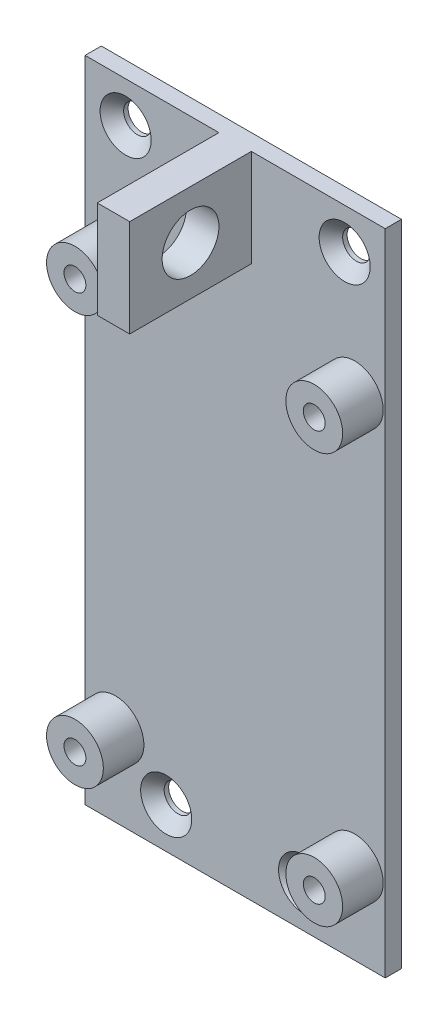
SolidWorks part; units mm, degrees
ref_plane "Plan de face" through (0, 0, 0) normal (0, 0, 1) x (1, 0, 0)
ref_plane "Plan de dessus" through (0, 0, 0) normal (0, 1, 0) x (1, 0, 0)
ref_plane "Plan de droite" through (0, 0, 0) normal (1, 0, 0) x (0, 0, -1)
sketch "Main-Sketch" plane through (0, 0, 0) normal (0, 0, 1) x (1, 0, 0)
  line L1 (0, 0) -> (37, 0)
  line L2 (0, 0) -> (0, 80)
  line L3 (0, 80) -> (37, 80)
  line L4 (37, 0) -> (37, 80)
  dimension "D1" = 37
  dimension "D2" = 80
extrude "Main-Extrusion" add sketch "Main-Sketch" along normal blind 2
sketch "Board-Fix-Sketch" plane through (0, 0, 2) normal (0, 0, 1) x (1, 0, 0)
  line L0 (0, 80) -> (0, 0) construction
  line L1 (37, 0) -> (37, 80) construction
  line L2 (0, 0) -> (37, 0) construction
  circle A0 centre (3.75, 10) radius 3.5
  circle A1 centre (33.25, 10) radius 3.5
  circle A2 centre (33.25, 60.5) radius 3.5
  circle A3 centre (3.75, 60.5) radius 3.5
  circle A4 centre (3.75, 10) radius 1.35
  circle A5 centre (33.25, 10) radius 1.35
  circle A6 centre (33.25, 60.5) radius 1.35
  circle A7 centre (3.75, 60.5) radius 1.35
  dimension "D4" = 7
  dimension "D5" = 10
  dimension "D7" = 2.7
  dimension "D1" = 3.75
  dimension "D2" = 3.75
  dimension "D3" = 50.5
  dimension "D6" = 29.5
extrude "Board-Fix" add sketch "Board-Fix-Sketch" along normal blind 5
hole_wizard "Fraisage pour vis à tête fraisée M31" positions "Esquisse3" profile "Esquisse4" countersink size "M3" standard "Ansi Metric" end condition through all
sketch "Esquisse3" plane through (0, 0, 2) normal (0, 0, 1) x (1, 0, 0)
  line L0 (0, 80) -> (0, 0) construction
  line L1 (0, 0) -> (37, 0) construction
  line L2 (37, 0) -> (37, 80) construction
  line L3 (37, 80) -> (0, 80) construction
  point P0 (10, 5)
  point P2 (27, 5)
  point P4 (32, 75)
  point P6 (5, 75)
  dimension "D1" = 10
  dimension "D2" = 5
  dimension "D3" = 10
  dimension "D4" = 5
  dimension "D5" = 5
  dimension "D6" = 5
  dimension "D7" = 5
  dimension "D8" = 27
  dimension "D9" = 70
sketch "Esquisse4" plane through (10, 5, 2) normal (1, 0, 0) x (0, -1, 0)
  line L0 (0, 0) -> (0, 2)
  line L1 (0, 2) -> (1.7, 2)
  line L2 (1.7, 2) -> (1.7, 1.45)
  line L3 (1.7, 1.45) -> (3.15, 0)
  line L5 (3.15, 0) -> (0, 0)
  line L6 (-1.7, 1.45) -> (-3.15, 0) construction
  line L11 (0, -6.35) -> (0, 107.95) construction
  dimension "Diamètre du perçage jusqu'au prochain" = 3.4
  dimension "Profondeur du perçage jusqu'au prochain" = 2
  dimension "Diamètre du fraisage entrant" = 6.3
  dimension "Angle du fraisage entrant" = 90
sketch "Jack-Fix-Sketch" plane through (0, 0, 2) normal (0, 0, 1) x (1, 0, 0)
  line L0 (37, 80) -> (0, 80) construction
  line L1 (16.5, 80) -> (20.5, 80)
  line L2 (16.5, 80) -> (16.5, 68)
  line L3 (16.5, 68) -> (20.5, 68)
  line L4 (20.5, 80) -> (20.5, 68)
  point P8 (18.5, 80)
  point P9 (18.5, 80)
  dimension "D1" = 4
  dimension "D2" = 12
extrude "Jack-Fix" add sketch "Jack-Fix-Sketch" along normal blind 15
sketch "Jack-Fix-Hole-Sketch" plane through (20.5, 0, 0) normal (1, 0, 0) x (0, 0, -1)
  line L0 (-17, 68) -> (-17, 80) construction
  line L1 (-17, 80) -> (-2, 80) construction
  circle A0 centre (-9.5, 74) radius 3.5
  point P5 (-17, 74)
  point P9 (-9.5, 80)
  dimension "D1" = 7
extrude "Jack-Fix-Hole" cut sketch "Jack-Fix-Hole-Sketch" against normal through all
